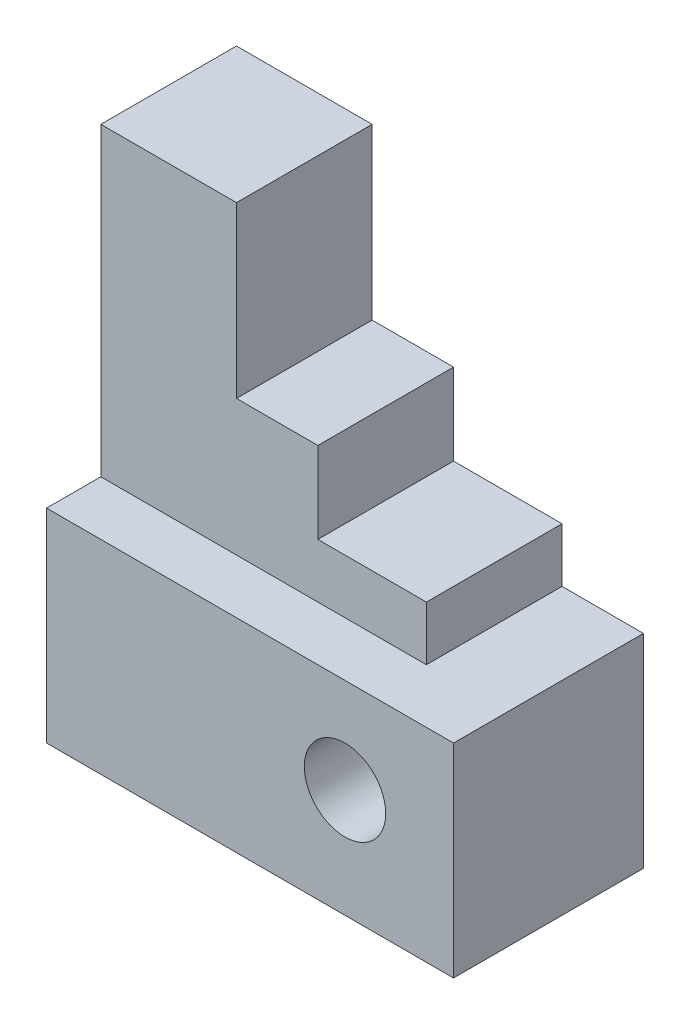
SolidWorks part; units mm, degrees
ref_plane "Alzado" through (0, 0, 0) normal (0, 0, 1) x (1, 0, 0)
ref_plane "Planta" through (0, 0, 0) normal (0, 1, 0) x (1, 0, 0)
ref_plane "Vista lateral" through (0, 0, 0) normal (1, 0, 0) x (0, 0, -1)
sketch "Croquis1" plane through (0, 0, 0) normal (0, 0, 1) x (1, 0, 0)
  line L0 (0, 3.6923) -> (0, 6.1775)
  line L2 (0, 0) -> (60, 0)
  line L3 (0, 0) -> (0, 30)
  line L4 (0, 30) -> (60, 30)
  line L5 (60, 0) -> (60, 30)
  line L6 (0, 30) -> (45.7988, 30)
  line L10 (0, 30) -> (48, 30)
  line L11 (0, 30) -> (0, 38)
  line L12 (32, 38) -> (48, 38)
  line L13 (48, 30) -> (48, 38)
  line L15 (0, 38) -> (0, 50)
  line L16 (20, 50) -> (32, 50)
  line L17 (32, 38) -> (32, 50)
  line L19 (0, 50) -> (0, 75)
  line L20 (0, 75) -> (20, 75)
  line L21 (20, 50) -> (20, 75)
  circle A0 centre (44, 16) radius 6
  point P19 (0, 0)
  dimension "D4" = 12
  dimension "D5" = 16
  dimension "D12" = 44
  dimension "D1" = 30
  dimension "D2" = 60
  dimension "D3" = 16
  dimension "D6" = 75
  dimension "D7" = 20
  dimension "D8" = 12
  dimension "D9" = 12
  dimension "D10" = 12
  dimension "D11" = 20
extrude "Saliente-Extruir1" add sketch "Croquis1" along normal blind 28 contours L2 L5 L4 L3 L0 A0 region at (29.0614, 14.933, 0)
extrude "Saliente-Extruir2" add sketch "Croquis1<5>" along normal blind 20 contours L16 L21 L20 L19 L15 L11 L4 L13 L12 L17 region at (16.0568, 48.2666, 0)
sketch "Croquis1<5>" plane through (0, 0, 0) normal (0, 0, 1) x (1, 0, 0) same geometry as "Croquis1"
sketch "Croquis2" plane through (0, 0, 0) normal (0, 0, 1) x (1, 0, 0)
